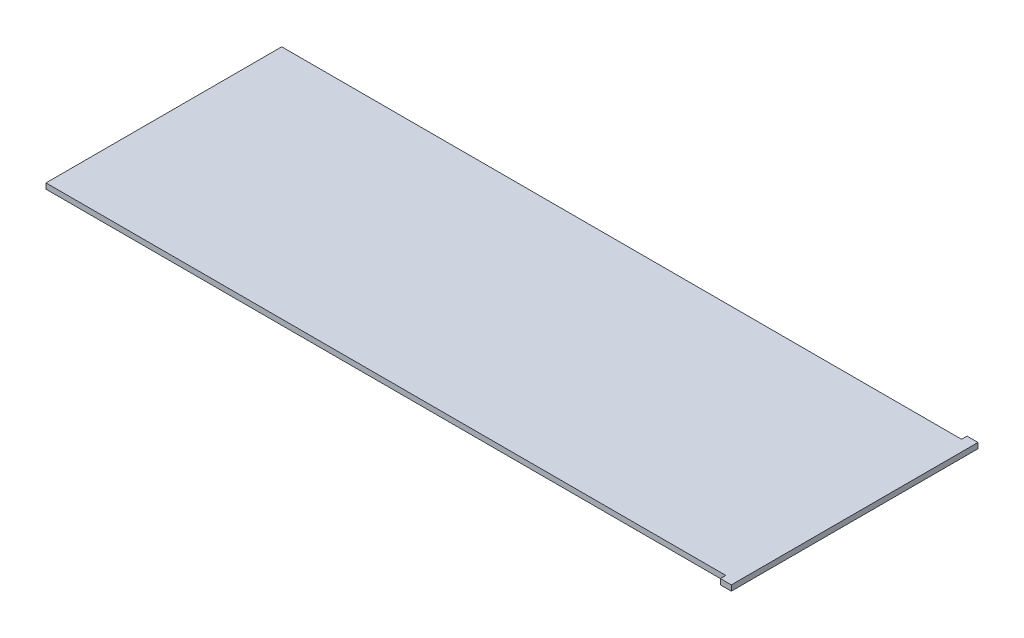
SolidWorks part; units mm, degrees
ref_plane "Front Plane" through (0, 0, 0) normal (0, 0, 1) x (1, 0, 0)
ref_plane "Top Plane" through (0, 0, 0) normal (0, 1, 0) x (1, 0, 0)
ref_plane "Right Plane" through (0, 0, 0) normal (1, 0, 0) x (0, 0, -1)
sketch "Sketch1" plane through (0, 0, 0) normal (0, 1, 0) x (1, 0, 0)
  line L1 (-200.025, 71.4375) -> (200.025, 71.4375)
  line L2 (-200.025, 71.4375) -> (-200.025, -71.4375)
  line L3 (-200.025, -71.4375) -> (200.025, -71.4375)
  line L4 (200.025, 71.4375) -> (200.025, -71.4375)
  line L5 (-200.025, 71.4375) -> (200.025, -71.4375) construction
  line L6 (-200.025, -71.4375) -> (200.025, 71.4375) construction
  line L7 (-200.025, -71.4375) -> (193.675, -71.4375)
  line L8 (-200.025, -71.4375) -> (-200.025, -68.2625)
  line L9 (-200.025, -68.2625) -> (193.675, -68.2625)
  line L10 (193.675, -71.4375) -> (193.675, -68.2625)
  line L11 (-200.025, 71.4375) -> (193.675, 71.4375)
  line L12 (-200.025, 71.4375) -> (-200.025, 68.2625)
  line L13 (-200.025, 68.2625) -> (193.675, 68.2625)
  line L14 (193.675, 71.4375) -> (193.675, 68.2625)
  point P0 (0, 0)
  dimension "D1" = 400.05
  dimension "D2" = 142.875
  dimension "D3" = 6.35
  dimension "D4" = 3.175
  dimension "D5" = 3.175
extrude "Boss-Extrude1" add sketch "Sketch1" along normal mid plane 3.175 contours L1 L14 L13 L2 L9 L10 L3 L4 region at (0.1452, 0, 0)
equation "\"D2@Sketch1\"   = 5.625in-(2*0.125in)"
equation "\"D1@Sketch1\"=16.00in-0.25in"
equation "\"D3@Sketch1\"=.25in"
